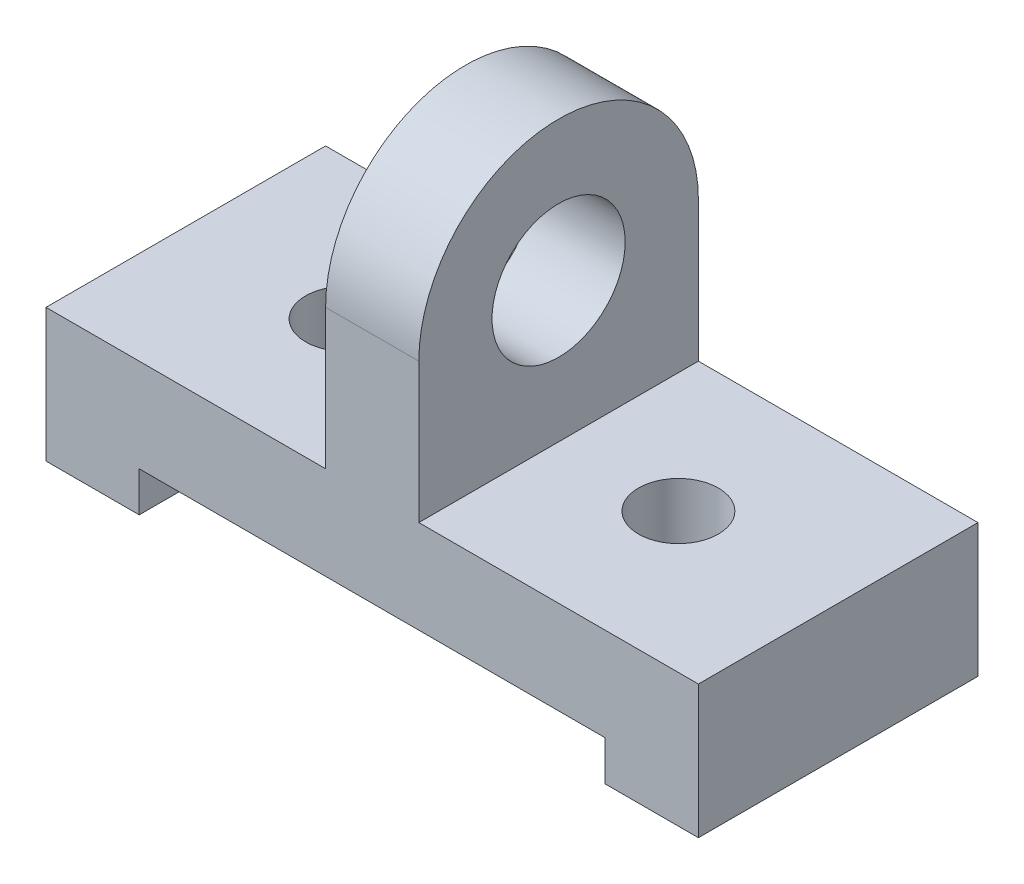
SolidWorks part; units mm, degrees
ref_plane "Front Plane" through (0, 0, 0) normal (0, 0, 1) x (1, 0, 0)
ref_plane "Top Plane" through (0, 0, 0) normal (0, 1, 0) x (1, 0, 0)
ref_plane "Right Plane" through (0, 0, 0) normal (1, 0, 0) x (0, 0, -1)
sketch "Sketch1" plane through (0, 0, 0) normal (0, 1, 0) x (1, 0, 0)
  line L1 (-49, 21) -> (49, 21)
  line L2 (-49, 21) -> (-49, -21)
  line L3 (-49, -21) -> (49, -21)
  line L4 (49, 21) -> (49, -21)
  line L5 (-49, 21) -> (49, -21) construction
  line L6 (-49, -21) -> (49, 21) construction
  point P1 (0, 0)
  dimension "D1" = 42
  dimension "D2" = 98
extrude "Boss-Extrude1" add sketch "Sketch1" along normal blind 20
sketch "Sketch2" plane through (0, 0, 21) normal (0, 0, 1) x (1, 0, 0)
  line L0 (-49, 0) -> (49, 0) construction
  line L1 (-35, 0) -> (35, 0)
  line L2 (-35, 0) -> (-35, 6)
  line L3 (-35, 6) -> (35, 6)
  line L4 (35, 0) -> (35, 6)
  dimension "D1" = 6
  dimension "D2" = 14
  dimension "D3" = 14
extrude "Cut-Extrude1" cut sketch "Sketch2" against normal through all
sketch "Sketch3" plane through (0, 20, 0) normal (0, 1, 0) x (1, 0, 0)
  line L0 (49, -21) -> (49, 21) construction
  line L1 (-49, 21) -> (-49, -21) construction
  line L2 (-49, -21) -> (49, -21) construction
  circle A1 centre (25, 0) radius 6
  circle A2 centre (-25, 0) radius 6
  point P10 (24.427, -0.6785)
  point P11 (-14.3013, 1.3049)
  dimension "D1" = 12
  dimension "D3" = 24
  dimension "D2" = 24
  dimension "D4" = 50
  dimension "D5" = 21
extrude "Cut-Extrude2" cut sketch "Sketch3" against normal up to surface (14 mm away) up to face at (0, 6, 0)
sketch "Sketch4" plane through (0, 0, 0) normal (1, 0, 0) x (0, 0, -1)
  line L1 (-21, 20) -> (21, 20)
  line L2 (-21, 20) -> (-21, 62)
  line L3 (-21, 62) -> (21, 62)
  line L4 (21, 20) -> (21, 62)
  dimension "D1" = 42
  dimension "D2" = 42
extrude "Boss-Extrude2" add sketch "Sketch4" along normal blind 7 and the other way blind 7
fillet "Fillet1" 2 edges at (0, 62, 21) (0, 62, -21) type full round first side face at (0, 18, 21) second side face at (0, 18, -21) middle face at (0, 62, 0)
sketch "Sketch5" plane through (7, 0, 0) normal (1, 0, 0) x (0, 0, -1)
  line L0 (-21, 20) -> (21, 20) construction
  circle A0 centre (0, 41) radius 10
  dimension "D1" = 21
  dimension "D2" = 20
extrude "Cut-Extrude3" cut sketch "Sketch5" against normal up to surface (14 mm away) up to face at (-7, 35.75, 0)
